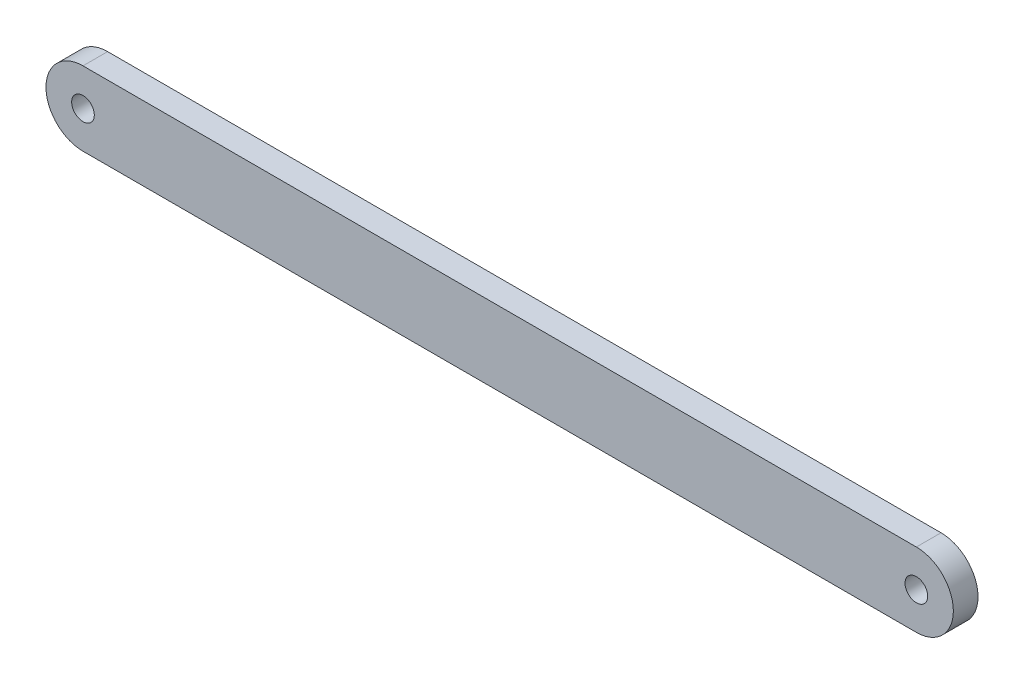
SolidWorks part; units mm, degrees
ref_plane "前视基准面" through (0, 0, 0) normal (0, 0, 1) x (1, 0, 0)
ref_plane "上视基准面" through (0, 0, 0) normal (0, 1, 0) x (1, 0, 0)
ref_plane "右视基准面" through (0, 0, 0) normal (1, 0, 0) x (0, 0, -1)
other "Configuration Table"
sketch "草图1" plane through (0, 0, 0) normal (0, 0, 1) x (1, 0, 0)
  line L1 (-84.5234, 7.5) -> (84.5234, 7.5)
  line L3 (-84.5234, -7.5) -> (84.5234, -7.5)
  line L5 (-84.5234, 7.5) -> (84.5234, -7.5) construction
  line L6 (-84.5234, -7.5) -> (84.5234, 7.5) construction
  arc A0 (-84.5234, 7.5) -> (-84.5234, -7.5) centre (-84.5234, 0) ccw
  arc A1 (84.5234, 7.5) -> (84.5234, -7.5) centre (84.5234, 0) cw
  circle A2 centre (-84.5234, 0) radius 2.3
  circle A3 centre (84.5234, 0) radius 2.3
  point P0 (0, 0)
  dimension "D1" = 4.6
  dimension "D2" = 4.6
  dimension "D3" = 169.0467
  dimension "D4" = 15
extrude "凸台-拉伸1" add sketch "草图1" along normal blind 5
equation "\"fi\"=4.6"
equation "\"D1@草图1\"=\"fi\""
equation "\"D2@草图1\"=\"fi\""
equation "\"b0\"= 75.6'ground"
equation "\"b5\"=(\"b2\"^2+\"b4\"^2)^0.5'斜边"
equation "\"D3@草图1\"=\"b5\""
equation "\"width\"=15"
equation "\"D4@草图1\"=\"width\""
equation "\"depth\"=5"
equation "\"D1@凸台-拉伸1\"=\"depth\""
equation "\"b1\"= \"b0\" *1.4/ 2'rocker"
equation "\"b2\"= \"b0\"'coupler"
equation "\"b3\"= \"b0\" / 2'coupler"
equation "\"b4\"= \"b0\" *2'leg"
equation "\"angle\"= 40*pi/180'ground水平夹角"
